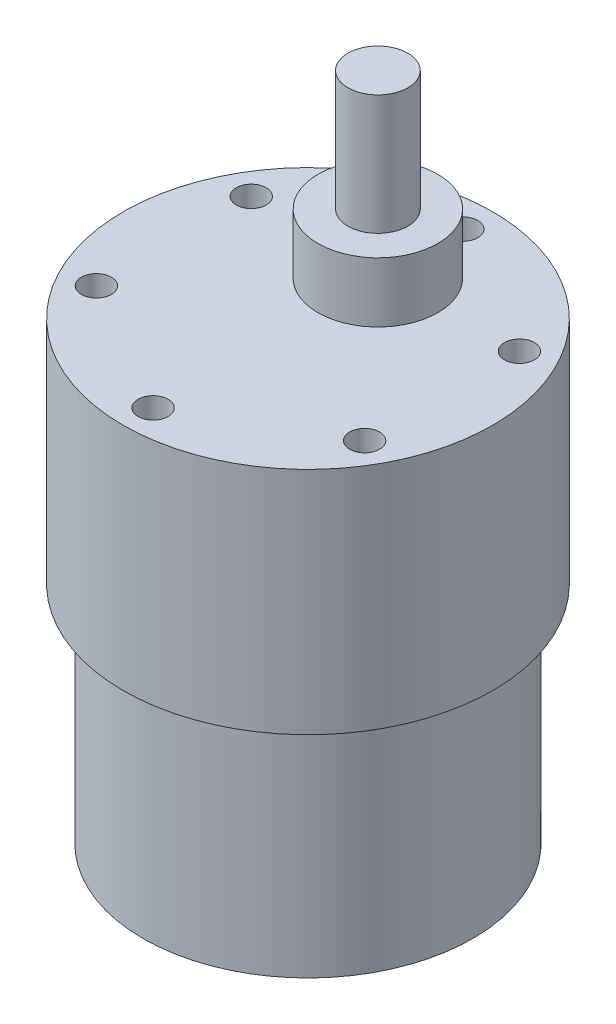
SolidWorks part; units mm, degrees
ref_plane "前视基准面" through (0, 0, 0) normal (0, 0, 1) x (1, 0, 0)
ref_plane "上视基准面" through (0, 0, 0) normal (0, 1, 0) x (1, 0, 0)
ref_plane "右视基准面" through (0, 0, 0) normal (1, 0, 0) x (0, 0, -1)
sketch "草图1" plane through (0, 0, 0) normal (0, 1, 0) x (1, 0, 0)
  circle A0 centre (0, 0) radius 18.5
  dimension "D1" = 37
extrude "凸台-拉伸1" add sketch "草图1" against normal blind 23
sketch "草图3" plane through (0, -23, 0) normal (0, -1, 0) x (1, 0, 0)
  circle A0 centre (0, 0) radius 16.5
  dimension "D1" = 33
extrude "凸台-拉伸2" add sketch "草图3" along normal blind 22.5
sketch "草图4" plane through (0, 0, 0) normal (0, 1, 0) x (1, 0, 0)
  circle A0 centre (0, 0) radius 15.5 construction
  circle A1 centre (0, 15.5) radius 1.5
  circle A2 centre (13.4234, 7.75) radius 1.5
  circle A3 centre (13.4234, -7.75) radius 1.5
  circle A4 centre (0, -15.5) radius 1.5
  circle A5 centre (-13.4234, -7.75) radius 1.5
  circle A6 centre (-13.4234, 7.75) radius 1.5
  point P17 (0, 0)
  dimension "D1" = 31
  dimension "D2" = 3
  dimension "D3" = 6
extrude "切除-拉伸1" cut sketch "草图4" against normal blind 15
sketch "草图5" plane through (0, 0, 0) normal (0, 1, 0) x (1, 0, 0)
  circle A0 centre (0, 7) radius 6
  dimension "D1" = 12
  dimension "D2" = 7
extrude "凸台-拉伸3" add sketch "草图5" along normal blind 6
sketch "草图6" plane through (0, 6, 0) normal (0, 1, 0) x (1, 0, 0)
  circle A0 centre (0, 7) radius 3
  circle A1 centre (0, 7) radius 6 construction
  dimension "D1" = 6
extrude "凸台-拉伸4" add sketch "草图6" along normal blind 12
